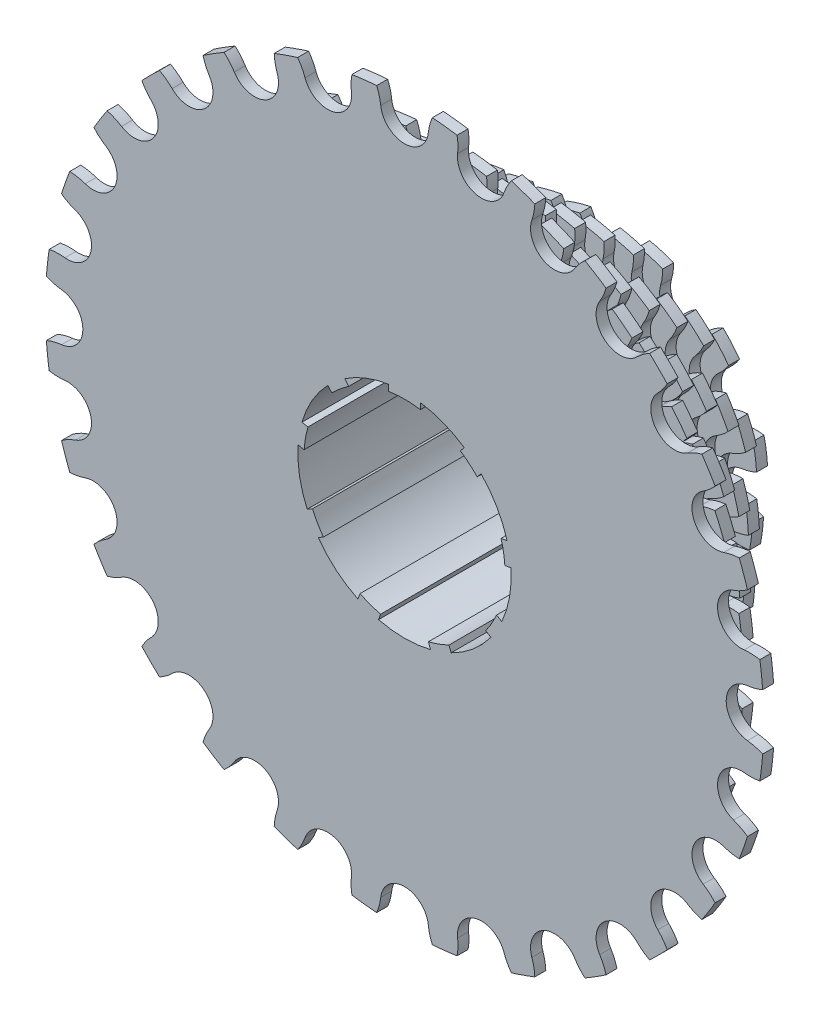
SolidWorks part; units mm, degrees
material "Acero aleado"
ref_plane "Alzado" through (0, 0, 0) normal (0, 0, 1) x (1, 0, 0)
ref_plane "Planta" through (0, 0, 0) normal (0, 1, 0) x (1, 0, 0)
ref_plane "Vista lateral" through (0, 0, 0) normal (1, 0, 0) x (0, 0, -1)
sketch "Sk_Nucleo" plane through (0, 0, 0) normal (0, 0, 1) x (1, 0, 0)
  line L0 (2.6, 17.3058) -> (2.6, 16.2939)
  line L1 (-2.6, 16.2939) -> (-2.6, 17.3058)
  line L2 (-9.8102, 14.4917) -> (-9.1638, 13.7213)
  line L3 (-11.9216, 11.4073) -> (-12.568, 12.1777)
  line L4 (-16.8302, 4.7954) -> (-15.8398, 4.6207)
  line L5 (-16.4649, 1.0754) -> (-17.4553, 1.2501)
  line L6 (-15.9751, -7.1447) -> (-15.1041, -6.6419)
  line L7 (-13.3041, -9.7596) -> (-14.1751, -10.2624)
  line L8 (-7.6451, -15.7418) -> (-7.3011, -14.7968)
  line L9 (-3.9182, -16.028) -> (-4.2622, -16.973)
  line L10 (4.2622, -16.973) -> (3.9182, -16.028)
  line L11 (7.3011, -14.7968) -> (7.6451, -15.7418)
  line L12 (14.1751, -10.2624) -> (13.3041, -9.7596)
  line L13 (15.1041, -6.6419) -> (15.9751, -7.1447)
  line L14 (17.4553, 1.2501) -> (16.4649, 1.0754)
  line L15 (15.8398, 4.6207) -> (16.8302, 4.7954)
  line L16 (12.568, 12.1777) -> (11.9216, 11.4073)
  line L17 (9.1638, 13.7213) -> (9.8102, 14.4917)
  circle A0 centre (0, 0) radius 18.5
  arc A1 (2.6, 16.2939) -> (-2.6, 16.2939) centre (0, 0) ccw
  arc A2 (-2.6, 17.3058) -> (-9.8102, 14.4917) centre (0, 0) ccw
  arc A3 (-9.1638, 13.7213) -> (-11.9216, 11.4073) centre (0, 0) ccw
  arc A4 (-12.568, 12.1777) -> (-16.8302, 4.7954) centre (0, 0) ccw
  arc A5 (-15.8398, 4.6207) -> (-16.4649, 1.0754) centre (0, 0) ccw
  arc A6 (-17.4553, 1.2501) -> (-15.9751, -7.1447) centre (0, 0) ccw
  arc A7 (-15.1041, -6.6419) -> (-13.3041, -9.7596) centre (0, 0) ccw
  arc A8 (-14.1751, -10.2624) -> (-7.6451, -15.7418) centre (0, 0) ccw
  arc A9 (-7.3011, -14.7968) -> (-3.9182, -16.028) centre (0, 0) ccw
  arc A10 (-4.2622, -16.973) -> (4.2622, -16.973) centre (0, 0) ccw
  arc A11 (3.9182, -16.028) -> (7.3011, -14.7968) centre (0, 0) ccw
  arc A12 (7.6451, -15.7418) -> (14.1751, -10.2624) centre (0, 0) ccw
  arc A13 (13.3041, -9.7596) -> (15.1041, -6.6419) centre (0, 0) ccw
  arc A14 (15.9751, -7.1447) -> (17.4553, 1.2501) centre (0, 0) ccw
  arc A15 (16.4649, 1.0754) -> (15.8398, 4.6207) centre (0, 0) ccw
  arc A16 (16.8302, 4.7954) -> (12.568, 12.1777) centre (0, 0) ccw
  arc A17 (11.9216, 11.4073) -> (9.1638, 13.7213) centre (0, 0) ccw
  arc A18 (9.8102, 14.4917) -> (2.6, 17.3058) centre (0, 0) ccw
  dimension "D1" = 37
extrude "Nucleo" add sketch "Sk_Nucleo" along normal blind 35.4
ref_axis "Eje_cassette" through (0, 0, -1.77) along (0, 0, 1)
sketch "Sk_Disco_0" plane through (0, 0, 0) normal (0, 0, 1) x (1, 0, 0)
  circle A0 centre (0, 0) radius 24.2105
  circle A1 centre (0, 0) radius 18.5
  dimension "D1" = 48.4209
  dimension "D2" = 37
extrude "Disco_0" add sketch "Sk_Disco_0" along normal blind 1.8
sketch "Sk_Hueco_0" plane through (0, 0, 0) normal (0, 0, 1) x (1, 0, 0)
  line L0 (0, 0) -> (0, 22.5391) construction
  line L1 (0, 0) -> (-12.1856, 18.9611) construction
  line L2 (0, 0) -> (12.1856, 18.9611) construction
  line L3 (0, 22.5391) -> (-12.1856, 18.9611) construction
  line L4 (0, 22.5391) -> (12.1856, 18.9611) construction
  arc A0 (-3.7686, 21.4326) -> (3.7686, 21.4326) centre (0, 22.5391) ccw
  arc A1 (-3.7686, 21.4326) -> (-6.2793, 25.4472) centre (-12.1856, 18.9611) ccw
  arc A2 (6.2793, 25.4472) -> (3.7686, 21.4326) centre (12.1856, 18.9611) ccw
  arc A3 (6.2793, 25.4472) -> (-6.2793, 25.4472) centre (0, 0) ccw
  dimension "D6" = 3.9277
  dimension "D7" = 26.2105
  dimension "D1" = 22.5391
  dimension "D2" = 22.5391
  dimension "D3" = 22.5391
  dimension "D4" = 32.727
  dimension "D5" = 32.727
extrude "Hueco_0" cut sketch "Sk_Hueco_0" along normal blind 1.8
pattern_circular "Matriz_0" count 11 over 360 about axis through (0, 0, -1.77) along (0, 0, 1) of "Hueco_0"
ref_plane "Plano_1" through (0, 0, 4.8) normal (0, 0, 1) x (1, 0, 0)
sketch "Sk_Disco_1" plane through (0, 0, 4.8) normal (0, 0, 1) x (1, 0, 0)
  circle A0 centre (0, 0) radius 28.3475
  circle A1 centre (0, 0) radius 18.5
  dimension "D2" = 37
  dimension "D1" = 56.6949
extrude "Disco_1" add sketch "Sk_Disco_1" along normal blind 1.8
sketch "Sk_Hueco_1" plane through (0, 0, 4.8) normal (0, 0, 1) x (1, 0, 0)
  line L0 (0, 0) -> (0, 26.534) construction
  line L1 (0, 0) -> (-12.331, 23.4947) construction
  line L2 (0, 0) -> (12.331, 23.4947) construction
  line L3 (0, 26.534) -> (-12.331, 23.4947) construction
  line L4 (0, 26.534) -> (12.331, 23.4947) construction
  arc A0 (-3.8135, 25.594) -> (3.8135, 25.594) centre (0, 26.534) ccw
  arc A1 (-3.8135, 25.594) -> (-6.1485, 29.7181) centre (-12.331, 23.4947) ccw
  arc A2 (6.1485, 29.7181) -> (3.8135, 25.594) centre (12.331, 23.4947) ccw
  arc A3 (6.1485, 29.7181) -> (-6.1485, 29.7181) centre (0, 0) ccw
  dimension "D6" = 3.9277
  dimension "D7" = 30.3475
  dimension "D1" = 26.534
  dimension "D2" = 26.534
  dimension "D3" = 26.534
  dimension "D4" = 27.692
  dimension "D5" = 27.692
extrude "Hueco_1" cut sketch "Sk_Hueco_1" along normal blind 1.8
pattern_circular "Matriz_1" count 13 over 360 about axis through (0, 0, -1.77) along (0, 0, 1) of "Hueco_1"
ref_plane "Plano_2" through (0, 0, 9.6) normal (0, 0, 1) x (1, 0, 0)
sketch "Sk_Disco_2" plane through (0, 0, 9.6) normal (0, 0, 1) x (1, 0, 0)
  circle A0 centre (0, 0) radius 32.4595
  circle A1 centre (0, 0) radius 18.5
  dimension "D2" = 37
  dimension "D1" = 64.919
extrude "Disco_2" add sketch "Sk_Disco_2" along normal blind 1.8
sketch "Sk_Hueco_2" plane through (0, 0, 9.6) normal (0, 0, 1) x (1, 0, 0)
  line L0 (0, 0) -> (0, 30.5418) construction
  line L1 (0, 0) -> (-12.4225, 27.9013) construction
  line L2 (0, 0) -> (12.4225, 27.9013) construction
  line L3 (0, 30.5418) -> (-12.4225, 27.9013) construction
  line L4 (0, 30.5418) -> (12.4225, 27.9013) construction
  arc A0 (-3.8418, 29.7252) -> (3.8418, 29.7252) centre (0, 30.5418) ccw
  arc A1 (-3.8418, 29.7252) -> (-6.0453, 33.9251) centre (-12.4225, 27.9013) ccw
  arc A2 (6.0453, 33.9251) -> (3.8418, 29.7252) centre (12.4225, 27.9013) ccw
  arc A3 (6.0453, 33.9251) -> (-6.0453, 33.9251) centre (0, 0) ccw
  dimension "D6" = 3.9277
  dimension "D7" = 34.4595
  dimension "D1" = 30.5418
  dimension "D2" = 30.5418
  dimension "D3" = 30.5418
  dimension "D4" = 24
  dimension "D5" = 24
extrude "Hueco_2" cut sketch "Sk_Hueco_2" along normal blind 1.8
pattern_circular "Matriz_2" count 15 over 360 about axis through (0, 0, -1.77) along (0, 0, 1) of "Hueco_2"
ref_plane "Plano_3" through (0, 0, 14.4) normal (0, 0, 1) x (1, 0, 0)
sketch "Sk_Disco_3" plane through (0, 0, 14.4) normal (0, 0, 1) x (1, 0, 0)
  circle A0 centre (0, 0) radius 36.5553
  circle A1 centre (0, 0) radius 18.5
  dimension "D2" = 37
  dimension "D1" = 73.1105
extrude "Disco_3" add sketch "Sk_Disco_3" along normal blind 1.8
sketch "Sk_Hueco_3" plane through (0, 0, 14.4) normal (0, 0, 1) x (1, 0, 0)
  line L0 (0, 0) -> (0, 34.5579) construction
  line L1 (0, 0) -> (-12.4838, 32.2243) construction
  line L2 (0, 0) -> (12.4838, 32.2243) construction
  line L3 (0, 34.5579) -> (-12.4838, 32.2243) construction
  line L4 (0, 34.5579) -> (12.4838, 32.2243) construction
  arc A0 (-3.8608, 33.8362) -> (3.8608, 33.8362) centre (0, 34.5579) ccw
  arc A1 (-3.8608, 33.8362) -> (-5.9623, 38.0915) centre (-12.4838, 32.2243) ccw
  arc A2 (5.9623, 38.0915) -> (3.8608, 33.8362) centre (12.4838, 32.2243) ccw
  arc A3 (5.9623, 38.0915) -> (-5.9623, 38.0915) centre (0, 0) ccw
  dimension "D6" = 3.9277
  dimension "D7" = 38.5553
  dimension "D1" = 34.5579
  dimension "D2" = 34.5579
  dimension "D3" = 34.5579
  dimension "D4" = 21.176
  dimension "D5" = 21.176
extrude "Hueco_3" cut sketch "Sk_Hueco_3" along normal blind 1.8
pattern_circular "Matriz_3" count 17 over 360 about axis through (0, 0, -1.77) along (0, 0, 1) of "Hueco_3"
ref_plane "Plano_4" through (0, 0, 19.2) normal (0, 0, 1) x (1, 0, 0)
sketch "Sk_Disco_4" plane through (0, 0, 19.2) normal (0, 0, 1) x (1, 0, 0)
  circle A0 centre (0, 0) radius 40.6399
  circle A1 centre (0, 0) radius 18.5
  dimension "D2" = 37
  dimension "D1" = 81.2798
extrude "Disco_4" add sketch "Sk_Disco_4" along normal blind 1.8
sketch "Sk_Hueco_4" plane through (0, 0, 19.2) normal (0, 0, 1) x (1, 0, 0)
  line L0 (0, 0) -> (0, 38.5796) construction
  line L1 (0, 0) -> (-12.5268, 36.4893) construction
  line L2 (0, 0) -> (12.5268, 36.4893) construction
  line L3 (0, 38.5796) -> (-12.5268, 36.4893) construction
  line L4 (0, 38.5796) -> (12.5268, 36.4893) construction
  arc A0 (-3.8741, 37.9332) -> (3.8741, 37.9332) centre (0, 38.5796) ccw
  arc A1 (-3.8741, 37.9332) -> (-5.8942, 42.2306) centre (-12.5268, 36.4893) ccw
  arc A2 (5.8942, 42.2306) -> (3.8741, 37.9332) centre (12.5268, 36.4893) ccw
  arc A3 (5.8942, 42.2306) -> (-5.8942, 42.2306) centre (0, 0) ccw
  dimension "D6" = 3.9277
  dimension "D7" = 42.6399
  dimension "D1" = 38.5796
  dimension "D2" = 38.5796
  dimension "D3" = 38.5796
  dimension "D4" = 18.947
  dimension "D5" = 18.947
extrude "Hueco_4" cut sketch "Sk_Hueco_4" along normal blind 1.8
pattern_circular "Matriz_4" count 19 over 360 about axis through (0, 0, -1.77) along (0, 0, 1) of "Hueco_4"
ref_plane "Plano_5" through (0, 0, 24) normal (0, 0, 1) x (1, 0, 0)
sketch "Sk_Disco_5" plane through (0, 0, 24) normal (0, 0, 1) x (1, 0, 0)
  circle A0 centre (0, 0) radius 44.7166
  circle A1 centre (0, 0) radius 18.5
  dimension "D2" = 37
  dimension "D1" = 89.4331
extrude "Disco_5" add sketch "Sk_Disco_5" along normal blind 1.8
sketch "Sk_Hueco_5" plane through (0, 0, 24) normal (0, 0, 1) x (1, 0, 0)
  line L0 (0, 0) -> (0, 42.6054) construction
  line L1 (0, 0) -> (-12.5582, 40.7125) construction
  line L2 (0, 0) -> (12.5582, 40.7125) construction
  line L3 (0, 42.6054) -> (-12.5582, 40.7125) construction
  line L4 (0, 42.6054) -> (12.5582, 40.7125) construction
  arc A0 (-3.8838, 42.02) -> (3.8838, 42.02) centre (0, 42.6054) ccw
  arc A1 (-3.8838, 42.02) -> (-5.8374, 46.3504) centre (-12.5582, 40.7125) ccw
  arc A2 (5.8374, 46.3504) -> (3.8838, 42.02) centre (12.5582, 40.7125) ccw
  arc A3 (5.8374, 46.3504) -> (-5.8374, 46.3504) centre (0, 0) ccw
  dimension "D6" = 3.9277
  dimension "D7" = 46.7166
  dimension "D1" = 42.6054
  dimension "D2" = 42.6054
  dimension "D3" = 42.6054
  dimension "D4" = 17.143
  dimension "D5" = 17.143
extrude "Hueco_5" cut sketch "Sk_Hueco_5" along normal blind 1.8
pattern_circular "Matriz_5" count 21 over 360 about axis through (0, 0, -1.77) along (0, 0, 1) of "Hueco_5"
ref_plane "Plano_6" through (0, 0, 28.8) normal (0, 0, 1) x (1, 0, 0)
sketch "Sk_Disco_6" plane through (0, 0, 28.8) normal (0, 0, 1) x (1, 0, 0)
  circle A0 centre (0, 0) radius 50.8209
  circle A1 centre (0, 0) radius 18.5
  dimension "D2" = 37
  dimension "D1" = 101.6418
extrude "Disco_6" add sketch "Sk_Disco_6" along normal blind 1.8
sketch "Sk_Hueco_6" plane through (0, 0, 28.8) normal (0, 0, 1) x (1, 0, 0)
  line L0 (0, 0) -> (0, 48.6492) construction
  line L1 (0, 0) -> (-12.5913, 46.9916) construction
  line L2 (0, 0) -> (12.5913, 46.9916) construction
  line L3 (0, 48.6492) -> (-12.5913, 46.9916) construction
  line L4 (0, 48.6492) -> (12.5913, 46.9916) construction
  arc A0 (-3.8941, 48.1366) -> (3.8941, 48.1366) centre (0, 48.6492) ccw
  arc A1 (-3.8941, 48.1366) -> (-5.7682, 52.505) centre (-12.5913, 46.9916) ccw
  arc A2 (5.7682, 52.505) -> (3.8941, 48.1366) centre (12.5913, 46.9916) ccw
  arc A3 (5.7682, 52.505) -> (-5.7682, 52.505) centre (0, 0) ccw
  dimension "D6" = 3.9277
  dimension "D7" = 52.8209
  dimension "D1" = 48.6492
  dimension "D2" = 48.6492
  dimension "D3" = 48.6492
  dimension "D4" = 15
  dimension "D5" = 15
extrude "Hueco_6" cut sketch "Sk_Hueco_6" along normal blind 1.8
pattern_circular "Matriz_6" count 24 over 360 about axis through (0, 0, -1.77) along (0, 0, 1) of "Hueco_6"
ref_plane "Plano_7" through (0, 0, 33.6) normal (0, 0, 1) x (1, 0, 0)
sketch "Sk_Disco_7" plane through (0, 0, 33.6) normal (0, 0, 1) x (1, 0, 0)
  circle A0 centre (0, 0) radius 58.9466
  circle A1 centre (0, 0) radius 18.5
  dimension "D2" = 37
  dimension "D1" = 117.8931
extrude "Disco_7" add sketch "Sk_Disco_7" along normal blind 1.8
sketch "Sk_Hueco_7" plane through (0, 0, 33.6) normal (0, 0, 1) x (1, 0, 0)
  line L0 (0, 0) -> (0, 56.7144) construction
  line L1 (0, 0) -> (-12.6201, 55.2925) construction
  line L2 (0, 0) -> (12.6201, 55.2925) construction
  line L3 (0, 56.7144) -> (-12.6201, 55.2925) construction
  line L4 (0, 56.7144) -> (12.6201, 55.2925) construction
  arc A0 (-3.903, 56.2747) -> (3.903, 56.2747) centre (0, 56.7144) ccw
  arc A1 (-3.903, 56.2747) -> (-5.6969, 60.6797) centre (-12.6201, 55.2925) ccw
  arc A2 (5.6969, 60.6797) -> (3.903, 56.2747) centre (12.6201, 55.2925) ccw
  arc A3 (5.6969, 60.6797) -> (-5.6969, 60.6797) centre (0, 0) ccw
  dimension "D6" = 3.9277
  dimension "D7" = 60.9466
  dimension "D1" = 56.7144
  dimension "D2" = 56.7144
  dimension "D3" = 56.7144
  dimension "D4" = 12.857
  dimension "D5" = 12.857
extrude "Hueco_7" cut sketch "Sk_Hueco_7" along normal blind 1.8
pattern_circular "Matriz_7" count 28 over 360 about axis through (0, 0, -1.77) along (0, 0, 1) of "Hueco_7"
equation "\"p\"= 12.7"
equation "\"Dr\"= 7.51"
equation "\"e\"= 1.8"
equation "\"Esp\"= 3.0"
equation "\"Desp\"= 37.0"
equation "\"Paso\"= \"e\" + \"Esp\""
equation "\"ri\"= 0.505 * \"Dr\" + 0.069 * \"Dr\" ^ ( 1 / 3 )"
equation "\"Z0\"= 11"
equation "\"D0\"= \"p\" / sin ( 180 / \"Z0\" )"
equation "\"De0\"= \"D0\" + \"p\" * ( 1 - 1.6 / \"Z0\" ) - \"Dr\""
equation "\"Ang0\"= 360 / \"Z0\""
equation "\"Z1\"= 13"
equation "\"D1\"= \"p\" / sin ( 180 / \"Z1\" )"
equation "\"De1\"= \"D1\" + \"p\" * ( 1 - 1.6 / \"Z1\" ) - \"Dr\""
equation "\"Ang1\"= 360 / \"Z1\""
equation "\"Z2\"= 15"
equation "\"D2\"= \"p\" / sin ( 180 / \"Z2\" )"
equation "\"De2\"= \"D2\" + \"p\" * ( 1 - 1.6 / \"Z2\" ) - \"Dr\""
equation "\"Ang2\"= 360 / \"Z2\""
equation "\"Z3\"= 17"
equation "\"D3\"= \"p\" / sin ( 180 / \"Z3\" )"
equation "\"De3\"= \"D3\" + \"p\" * ( 1 - 1.6 / \"Z3\" ) - \"Dr\""
equation "\"Ang3\"= 360 / \"Z3\""
equation "\"Z4\"= 19"
equation "\"D4\"= \"p\" / sin ( 180 / \"Z4\" )"
equation "\"De4\"= \"D4\" + \"p\" * ( 1 - 1.6 / \"Z4\" ) - \"Dr\""
equation "\"Ang4\"= 360 / \"Z4\""
equation "\"Z5\"= 21"
equation "\"D5\"= \"p\" / sin ( 180 / \"Z5\" )"
equation "\"De5\"= \"D5\" + \"p\" * ( 1 - 1.6 / \"Z5\" ) - \"Dr\""
equation "\"Ang5\"= 360 / \"Z5\""
equation "\"Z6\"= 24"
equation "\"D6\"= \"p\" / sin ( 180 / \"Z6\" )"
equation "\"De6\"= \"D6\" + \"p\" * ( 1 - 1.6 / \"Z6\" ) - \"Dr\""
equation "\"Ang6\"= 360 / \"Z6\""
equation "\"Z7\"= 28"
equation "\"D7\"= \"p\" / sin ( 180 / \"Z7\" )"
equation "\"De7\"= \"D7\" + \"p\" * ( 1 - 1.6 / \"Z7\" ) - \"Dr\""
equation "\"Ang7\"= 360 / \"Z7\""
equation "\"D1@Sk_Nucleo\" = \"Desp\""
equation "\"D1@Nucleo\" = 7 * \"Paso\" + \"e\""
equation "\"D1@Sk_Disco_0\" = \"De0\""
equation "\"D2@Sk_Disco_0\" = \"Desp\""
equation "\"D1@Disco_0\" = \"e\""
equation "\"D1@Sk_Hueco_0\" = \"D0\" / 2"
equation "\"D2@Sk_Hueco_0\" = \"D0\" / 2"
equation "\"D3@Sk_Hueco_0\" = \"D0\" / 2"
equation "\"D4@Sk_Hueco_0\" = \"Ang0\""
equation "\"D5@Sk_Hueco_0\" = \"Ang0\""
equation "\"D6@Sk_Hueco_0\" = \"ri\""
equation "\"D7@Sk_Hueco_0\" = \"De0\" / 2 + 2"
equation "\"D1@Hueco_0\" = \"e\""
equation "\"D1@Matriz_0\" = \"Z0\""
equation "\"D1@Sk_Disco_1\" = \"De1\""
equation "\"D2@Sk_Disco_1\" = \"Desp\""
equation "\"D1@Disco_1\" = \"e\""
equation "\"D1@Sk_Hueco_1\" = \"D1\" / 2"
equation "\"D2@Sk_Hueco_1\" = \"D1\" / 2"
equation "\"D3@Sk_Hueco_1\" = \"D1\" / 2"
equation "\"D4@Sk_Hueco_1\" = \"Ang1\""
equation "\"D5@Sk_Hueco_1\" = \"Ang1\""
equation "\"D6@Sk_Hueco_1\" = \"ri\""
equation "\"D7@Sk_Hueco_1\" = \"De1\" / 2 + 2"
equation "\"D1@Hueco_1\" = \"e\""
equation "\"D1@Matriz_1\" = \"Z1\""
equation "\"D1@Sk_Disco_2\" = \"De2\""
equation "\"D2@Sk_Disco_2\" = \"Desp\""
equation "\"D1@Disco_2\" = \"e\""
equation "\"D1@Sk_Hueco_2\" = \"D2\" / 2"
equation "\"D2@Sk_Hueco_2\" = \"D2\" / 2"
equation "\"D3@Sk_Hueco_2\" = \"D2\" / 2"
equation "\"D4@Sk_Hueco_2\" = \"Ang2\""
equation "\"D5@Sk_Hueco_2\" = \"Ang2\""
equation "\"D6@Sk_Hueco_2\" = \"ri\""
equation "\"D7@Sk_Hueco_2\" = \"De2\" / 2 + 2"
equation "\"D1@Hueco_2\" = \"e\""
equation "\"D1@Matriz_2\" = \"Z2\""
equation "\"D1@Sk_Disco_3\" = \"De3\""
equation "\"D2@Sk_Disco_3\" = \"Desp\""
equation "\"D1@Disco_3\" = \"e\""
equation "\"D1@Sk_Hueco_3\" = \"D3\" / 2"
equation "\"D2@Sk_Hueco_3\" = \"D3\" / 2"
equation "\"D3@Sk_Hueco_3\" = \"D3\" / 2"
equation "\"D4@Sk_Hueco_3\" = \"Ang3\""
equation "\"D5@Sk_Hueco_3\" = \"Ang3\""
equation "\"D6@Sk_Hueco_3\" = \"ri\""
equation "\"D7@Sk_Hueco_3\" = \"De3\" / 2 + 2"
equation "\"D1@Hueco_3\" = \"e\""
equation "\"D1@Matriz_3\" = \"Z3\""
equation "\"D1@Sk_Disco_4\" = \"De4\""
equation "\"D2@Sk_Disco_4\" = \"Desp\""
equation "\"D1@Disco_4\" = \"e\""
equation "\"D1@Sk_Hueco_4\" = \"D4\" / 2"
equation "\"D2@Sk_Hueco_4\" = \"D4\" / 2"
equation "\"D3@Sk_Hueco_4\" = \"D4\" / 2"
equation "\"D4@Sk_Hueco_4\" = \"Ang4\""
equation "\"D5@Sk_Hueco_4\" = \"Ang4\""
equation "\"D6@Sk_Hueco_4\" = \"ri\""
equation "\"D7@Sk_Hueco_4\" = \"De4\" / 2 + 2"
equation "\"D1@Hueco_4\" = \"e\""
equation "\"D1@Matriz_4\" = \"Z4\""
equation "\"D1@Sk_Disco_5\" = \"De5\""
equation "\"D2@Sk_Disco_5\" = \"Desp\""
equation "\"D1@Disco_5\" = \"e\""
equation "\"D1@Sk_Hueco_5\" = \"D5\" / 2"
equation "\"D2@Sk_Hueco_5\" = \"D5\" / 2"
equation "\"D3@Sk_Hueco_5\" = \"D5\" / 2"
equation "\"D4@Sk_Hueco_5\" = \"Ang5\""
equation "\"D5@Sk_Hueco_5\" = \"Ang5\""
equation "\"D6@Sk_Hueco_5\" = \"ri\""
equation "\"D7@Sk_Hueco_5\" = \"De5\" / 2 + 2"
equation "\"D1@Hueco_5\" = \"e\""
equation "\"D1@Matriz_5\" = \"Z5\""
equation "\"D1@Sk_Disco_6\" = \"De6\""
equation "\"D2@Sk_Disco_6\" = \"Desp\""
equation "\"D1@Disco_6\" = \"e\""
equation "\"D1@Sk_Hueco_6\" = \"D6\" / 2"
equation "\"D2@Sk_Hueco_6\" = \"D6\" / 2"
equation "\"D3@Sk_Hueco_6\" = \"D6\" / 2"
equation "\"D4@Sk_Hueco_6\" = \"Ang6\""
equation "\"D5@Sk_Hueco_6\" = \"Ang6\""
equation "\"D6@Sk_Hueco_6\" = \"ri\""
equation "\"D7@Sk_Hueco_6\" = \"De6\" / 2 + 2"
equation "\"D1@Hueco_6\" = \"e\""
equation "\"D1@Matriz_6\" = \"Z6\""
equation "\"D1@Sk_Disco_7\" = \"De7\""
equation "\"D2@Sk_Disco_7\" = \"Desp\""
equation "\"D1@Disco_7\" = \"e\""
equation "\"D1@Sk_Hueco_7\" = \"D7\" / 2"
equation "\"D2@Sk_Hueco_7\" = \"D7\" / 2"
equation "\"D3@Sk_Hueco_7\" = \"D7\" / 2"
equation "\"D4@Sk_Hueco_7\" = \"Ang7\""
equation "\"D5@Sk_Hueco_7\" = \"Ang7\""
equation "\"D6@Sk_Hueco_7\" = \"ri\""
equation "\"D7@Sk_Hueco_7\" = \"De7\" / 2 + 2"
equation "\"D1@Hueco_7\" = \"e\""
equation "\"D1@Matriz_7\" = \"Z7\""
